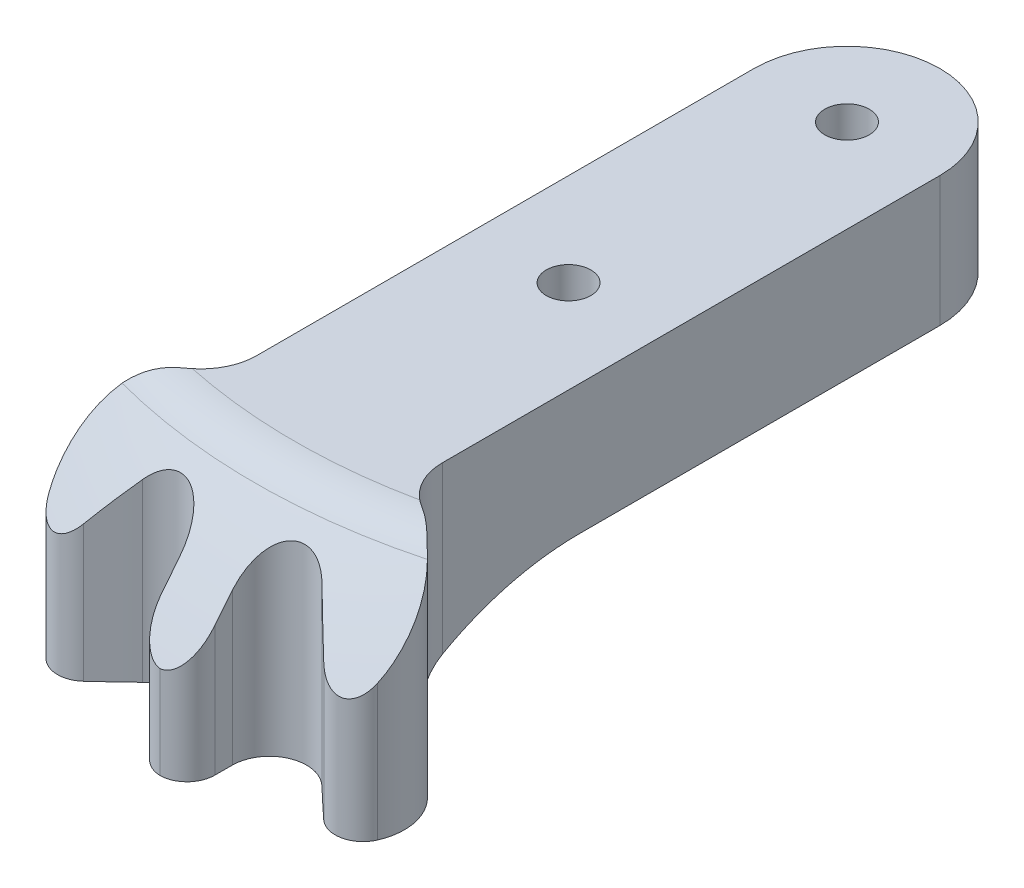
SolidWorks part; units mm, degrees
material "ABS"
ref_plane "Plan de face" through (0, 0, 0) normal (0, 0, 1) x (1, 0, 0)
ref_plane "Plan de dessus" through (0, 0, 0) normal (0, 1, 0) x (1, 0, 0)
ref_plane "Plan de droite" through (0, 0, 0) normal (1, 0, 0) x (0, 0, -1)
sketch "Esquisse1" plane through (0, 0, 0) normal (0, 1, 0) x (1, 0, 0)
  line L0 (0, -115) -> (0, -130) construction
  line L1 (5, -115) -> (5, -146)
  line L2 (-5, -115) -> (-5, -146)
  line L3 (-5, -146) -> (5, -146)
  circle A0 centre (0, -115) radius 1.2
  circle A1 centre (0, -130) radius 1.2
  arc A2 (5, -115) -> (-5, -115) centre (0, -115) ccw
  dimension "D1" = 15
  dimension "D2" = 115
  dimension "D3" = 2.4
  dimension "D5" = 16
  dimension "D4" = 10
extrude "Boss.-Extru.1" add sketch "Esquisse1" against normal blind 12
sketch "Esquisse2" plane through (0, 0, 0) normal (0, 1, 0) x (1, 0, 0)
  line L0 (0, 0) -> (0, -151) construction
  line L2 (-106.7731, -106.7731) -> (0, 0) construction
  circle A0 centre (-3.26, -149.1) radius 1.5 construction
  arc A1 (-7.6857, -158.6211) -> (-3.4503, -149.5624) centre (-106.7731, -106.7731) ccw construction
  arc A2 (-11.4529, -153.9512) -> (-4.8366, -148.1208) centre (-75.0791, -75.0791) ccw
  arc A3 (-1.6957, -158.967) -> (-1.4503, -149.5512) centre (-150.381, -150.381) ccw
  arc A4 (-11.4529, -153.9512) -> (-1.6957, -158.967) centre (-7.6857, -158.6211) ccw
  arc A5 (-1.4503, -149.5512) -> (-4.8366, -148.1208) centre (-3.4503, -149.5624) ccw
  arc A6 (2.2977, -159.1976) -> (2.5496, -149.5289) centre (-150.381, -150.381) ccw
  arc A7 (2.5496, -149.5289) -> (-7.6092, -145.2377) centre (-3.4503, -149.5624) ccw
  arc A8 (-13.9644, -150.838) -> (-7.6092, -145.2377) centre (-75.0791, -75.0791) ccw
  arc A9 (-13.9644, -150.838) -> (2.2977, -159.1976) centre (-7.6857, -158.6211) ccw
  dimension "D1" = 149.1
  dimension "D2" = 3.26
  dimension "D5" = 3
  dimension "D6" = 2
  dimension "D7" = 10
  dimension "D8" = 6
  dimension "D3" = 45
  dimension "D4" = 151
  dimension "D9" = 4
extrude "Boss.-Extru.2" add sketch "Esquisse2" against normal up to surface (12 mm away) up to face at (0, -12, 131.2)
sketch "Esquisse3" plane through (0, 0, 0) normal (0, 1, 0) x (1, 0, 0)
  line L0 (-13, -140.0302) -> (-13, -110)
  line L1 (-13, -110) -> (0, -110)
  line L2 (0, -110) -> (0, -153.0302)
  arc A0 (-13, -140.0302) -> (0, -153.0302) centre (0, -140.0302) ccw
  arc A1 (-1.4503, -149.5512) -> (-4.8366, -148.1208) centre (-3.4503, -149.5624) ccw construction
  arc A2 (-11.4529, -153.9512) -> (-1.6957, -158.967) centre (-7.6857, -158.6211) ccw construction
  circle A3 centre (-106.7731, -106.7731) radius 111.8326 construction
  arc A5 (5, -115) -> (-5, -115) centre (0, -115) ccw construction
  point P2 (-7.6857, -158.6211)
  point P4 (-3.4503, -149.5624)
  dimension "D1" = 151
  dimension "D2" = 13
extrude "Enlèv. mat.-Extru.1" cut sketch "Esquisse3" against normal through all flip side to cut
fillet "Congé2" radius 3 2 edges at (-5, -6, 143.766) (-10.4052, -6, 147.8232)
fillet "Congé1" radius 1.5 1 edges at (-7.5354, -6, 150.6235)
sketch "Esquisse5" plane through (0, 0, 0) normal (1, 0, 0) x (0, 0, -1)
  line L0 (-113.8, 0) -> (-116.2, 0) construction
  line L1 (-146, -12) -> (-115, -12)
  line L2 (-115, 0) -> (-115, -7) construction
  line L3 (-115, -7) -> (-135, -7)
  line L4 (-116.2, -12) -> (-113.8, -12) construction
  line L5 (-115, -7) -> (-115, -12)
  line L7 (-128.8, 0) -> (-131.2, 0) construction
  line L8 (-131.2, -12) -> (-128.8, -12) construction
  line L9 (-146, 0) -> (-160, 0)
  line L10 (-160, 0) -> (-160, -32.619)
  line L12 (-153.0302, 0) -> (-131.2, 0) construction
  arc A0 (-146, 0) -> (-160, -32.619) centre (-115, -32.619) ccw
  arc A1 (-146, -12) -> (-135, -7) centre (-135, -21.6) cw
  point P13 (-130, 0)
  point P16 (-130, -12)
  dimension "D1" = 16
  dimension "D3" = 14.6
  dimension "D5" = 31
  dimension "D7" = 45
  dimension "D2" = 7
  dimension "D4" = 5
  dimension "D6" = 45
revolve "Enlèvement de matière-Révolution1" cut sketch "Esquisse5" angle 360 about L2
mirror "Symétrie1" about plane through (0, 0, 0) normal (1, 0, 0) of bodies 105
sketch "Esquisse7" plane through (5, 0, 0) normal (1, 0, 0) x (0, 0, -1)
  line L0 (-115, 0) -> (-141.7971, 0) construction
  line L1 (-152.9468, -12) -> (-152, -12)
  line L2 (-152.9468, -12) -> (-152.9468, 0)
  line L3 (-152.9468, 0) -> (-152, 0)
  line L4 (-152, -12) -> (-152, 0)
  line L5 (-115, -7) -> (-115, 0) construction
  dimension "D1" = 37
extrude "Enlèv. mat.-Extru.5" cut sketch "Esquisse7" against normal blind 15
fillet "Congé3" radius 1.5 2 edges at (-1.4568, -9.524, 152) (1.4568, -9.524, 152)
sketch "Esquisse6" plane through (0, -7, 0) normal (0, -1, 0) x (1, 0, 0)
  line L1 (2.75, 116.5877) -> (0, 118.1754)
  line L2 (0, 118.1754) -> (-2.75, 116.5877)
  line L3 (-2.75, 116.5877) -> (-2.75, 113.4123)
  line L4 (-2.75, 113.4123) -> (0, 111.8246)
  line L5 (0, 111.8246) -> (2.75, 113.4123)
  line L6 (2.75, 113.4123) -> (2.75, 116.5877)
  line L7 (2.75, 131.5877) -> (0, 133.1754)
  line L8 (0, 133.1754) -> (-2.75, 131.5877)
  line L9 (-2.75, 131.5877) -> (-2.75, 128.4123)
  line L10 (-2.75, 128.4123) -> (0, 126.8246)
  line L11 (0, 126.8246) -> (2.75, 128.4123)
  line L12 (2.75, 128.4123) -> (2.75, 131.5877)
  circle A0 centre (0, 115) radius 2.75 construction
  circle A1 centre (0, 130) radius 2.75 construction
  dimension "D1" = 5.5
extrude "Enlèv. mat.-Extru.3" cut sketch "Esquisse6" against normal blind 2
fillet "Congé4" radius 3 16 edges at (-7.8881, -12, 145.5048) (-7.5309, -12, 145.1637) (0, -12, 146) (0, 0, 146) (-6.985, 0, 144.7141) (-8.8107, -1.8697, 146.652) (7.8881, -12, 145.5048) (7.5309, -12, 145.1637) (6.985, 0, 144.7141) (8.8107, -1.8697, 146.652)
